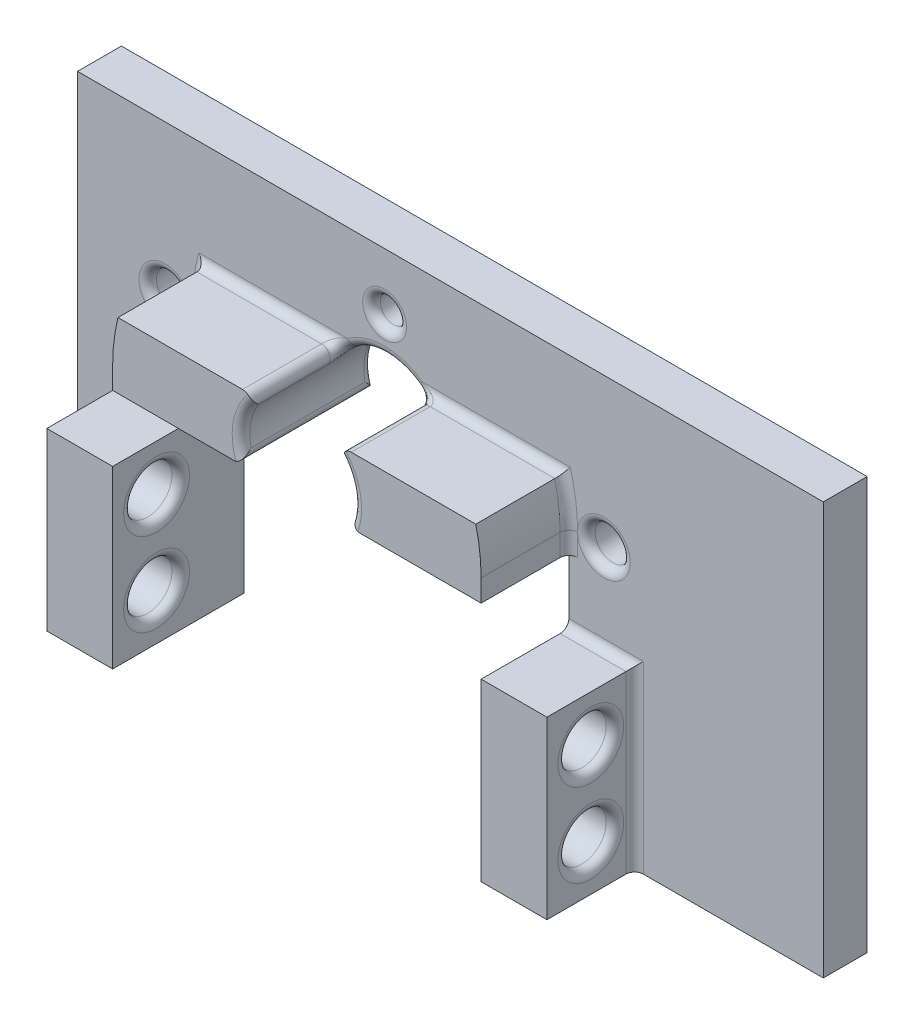
SolidWorks part; units mm, degrees
ref_plane "Front Plane" through (0, 0, 0) normal (0, 0, 1) x (1, 0, 0)
ref_plane "Top Plane" through (0, 0, 0) normal (0, 1, 0) x (1, 0, 0)
ref_plane "Right Plane" through (0, 0, 0) normal (1, 0, 0) x (0, 0, -1)
sketch "Base" plane through (0, 0, 0) normal (0, 0, 1) x (1, 0, 0)
  line L0 (0, 21) -> (0, -21) construction
  line L1 (50, 0) -> (-35, 0) construction
  line L3 (-35, 30) -> (50, 30)
  line L4 (-35, 30) -> (-35, -30)
  line L5 (-35, -30) -> (50, -30)
  line L6 (50, 30) -> (50, -30)
  line L7 (0, 0) -> (0, -30) construction
  circle A0 centre (25, 0) radius 2
  circle A1 centre (0, 0) radius 21
  circle A2 centre (-25, 0) radius 2
  dimension "D1" = 42
  dimension "D2" = 30
  dimension "D3" = 4
  dimension "D4" = 25
  dimension "D5" = 85
  dimension "D6" = 50
sketch "Sketch2" plane through (0, 0, 0) normal (0, 0, 1) x (1, 0, 0)
  line L0 (0, 21) -> (0, -21) construction
  line L1 (50, 0) -> (-35, 0) construction
  line L3 (-35, 30) -> (50, 30) construction
  line L4 (-35, 30) -> (-35, -30) construction
  line L5 (-35, -30) -> (50, -30) construction
  line L6 (50, 30) -> (50, -30) construction
  line L7 (0, 0) -> (0, -30) construction
  line L8 (-30, 12) -> (30, 12)
  line L9 (-30, 12) -> (-30, -20)
  line L10 (-30, -20) -> (30, -20)
  line L11 (30, 12) -> (30, -20)
  circle A0 centre (25, 0) radius 2.5
  circle A1 centre (0, 0) radius 21 construction
  circle A2 centre (-25, 0) radius 2.5
  circle A3 centre (0, 0) radius 6.375
  circle A4 centre (25, -15) radius 2.5
  circle A5 centre (-25, -15) radius 2.5
  circle A6 centre (10.375, 0) radius 1.5
  circle A7 centre (-10.375, 0) radius 1.5
  circle A8 centre (10.375, 0) radius 3.75
  circle A9 centre (-10.375, 0) radius 3.75
  point P25 (25, -17.5)
  point P26 (27.5, -15)
  point P29 (0, -20)
  point P32 (8.875, 0)
  point P33 (6.375, 0)
  point P35 (6.625, 0)
  dimension "D1" = 42
  dimension "D2" = 30
  dimension "D3" = 5
  dimension "D7" = 12.75
  dimension "D11" = 5
  dimension "D14" = 3
  dimension "D8" = 2.5
  dimension "D4" = 25
  dimension "D5" = 85
  dimension "D6" = 50
  dimension "D9" = 15
  dimension "D10" = 25
  dimension "D12" = 2.5
  dimension "D13" = 2.5
  dimension "D15" = 2.25
sketch "Sketch3" plane through (0, 0, 0) normal (0, 0, 1) x (1, 0, 0)
  line L0 (0, 21) -> (0, -21) construction
  line L1 (50, 0) -> (-35, 0) construction
  line L2 (21, 0) -> (21, -30)
  line L3 (-35, 30) -> (50, 30)
  line L4 (-35, 30) -> (-35, -30)
  line L5 (-35, -30) -> (50, -30)
  line L6 (50, 30) -> (50, -30)
  line L7 (0, 0) -> (0, -30) construction
  line L8 (-21, 0) -> (-21, -30)
  line L9 (-20.009, 6.375) -> (20.009, 6.375)
  line L10 (21, -10) -> (28.5, -10)
  line L11 (28.5, -10) -> (28.5, -30)
  line L12 (28.5, -30) -> (21, -30)
  line L13 (-21, -10) -> (-28.5, -10)
  line L14 (-28.5, -10) -> (-28.5, -30)
  line L15 (-28.5, -30) -> (-21, -30)
  line L16 (-35, 17) -> (50, 17)
  line L17 (-21, -2.5) -> (21, -2.5)
  line L18 (-20.3961, 5) -> (-3.9548, 5)
  line L19 (20.3961, 5) -> (3.9548, 5)
  circle A0 centre (25, 0) radius 2
  circle A1 centre (0, 0) radius 21 construction
  circle A2 centre (-25, 0) radius 2
  arc A3 (-21, 0) -> (-20.009, 6.375) centre (0, 0) cw
  circle A4 centre (0, 0) radius 6.375
  arc A5 (21, 0) -> (20.009, 6.375) centre (0, 0) ccw
  circle A6 centre (0, 10.5) radius 1.5
  point P34 (0, 9)
  point P35 (0, 6.375)
  point P38 (0, 12)
  dimension "D1" = 42
  dimension "D2" = 30
  dimension "D3" = 4
  dimension "D7" = 12.75
  dimension "D11" = 3
  dimension "D12" = 10.5
  dimension "D4" = 25
  dimension "D5" = 85
  dimension "D6" = 50
  dimension "D8" = 10
  dimension "D9" = 7.5
  dimension "D10" = 20
  dimension "D13" = 5
  dimension "D14" = 2.5
  dimension "D15" = 7.5
extrude "Boss-Extrude1" add sketch "Sketch3" against normal blind 5 contours A5 L2 L10 L11 L12 L5 L6 L3 L4 L8 L15 L14 L13 A3 L9 A6 A0 A2 | L14 L15 L8 L13 | L12 L11 L10 L2 | A4 L9 A3 L8 L17 | L2 A5 L9 A4 L17 | A4 L9 A3 L18 | L19 A5 L9 A4 region at (21.8128, 2.6346, 0) region at (13.3361, 1.2992, 0) region at (11.4312, 5.7053, 0) region at (24.75, -20, 0) region at (-13.3361, 1.2992, 0) region at (-11.4312, 5.7053, 0) region at (-24.75, -20, 0)
extrude "Boss-Extrude2" add sketch "Sketch3<4>" along normal blind 10 contours L14 L15 L8 L13 | L12 L11 L10 L2 region at (24.75, -20, 0) region at (-24.75, -20, 0)
sketch "Sketch3<4>" plane through (0, 0, 0) normal (0, 0, 1) x (1, 0, 0) same geometry as "Sketch3"
sketch "Sketch4" plane through (28.5, 0, 0) normal (1, 0, 0) x (0, 0, -1)
  line L0 (-5, -10) -> (-5, -30) construction
  line L2 (-10, -10) -> (0, -10) construction
  line L4 (-10, -30) -> (0, -30) construction
  line L5 (-10, -20) -> (0, -20) construction
  line L6 (-10, -10) -> (-10, -30) construction
  line L7 (0, -10) -> (0, -30) construction
  circle A0 centre (-5, -15.25) radius 2.75
  circle A1 centre (-5, -24.75) radius 2.75
  point P14 (-5, -12.5)
  dimension "D1" = 5.5
  dimension "D2" = 2.5
extrude "Cut-Extrude1" cut sketch "Sketch4" against normal up to surface (57 mm away) up to face at (-28.5, -17.5, 6.25)
extrude "Boss-Extrude3" add sketch "Sketch3<5>" along normal blind 10 contours L2 A5 L19 A4 L17 | A4 L18 A3 L8 L17 region at (13.3361, 1.2992, 0) region at (-13.3361, 1.2992, 0)
sketch "Sketch3<5>" plane through (0, 0, 0) normal (0, 0, 1) x (1, 0, 0) same geometry as "Sketch3"
fillet "Fillet1" radius 1 10 edges at (24.75, -10, 0) (28.5, -20, 0) (21, -1.25, 0) (20.8485, 2.5182, 0) (12.1755, 5, 0) (-21, -1.25, 0) (-20.8485, 2.5182, 0) (-12.1755, 5, 0)
fillet "Fillet2" radius 1 10 edges at (3.6072, 5.2563, 0.3315) (0, 6.375, 0) (-3.8026, 5.1167, 0.5311) (0, 6.375, -5) (-5.8644, -2.5, 2.5) (5.8644, -2.5, 2.5) (6.1779, 1.5729, 10) (-6.1779, 1.5729, 10) (3.9548, 5, 5.5) (-3.9548, 5, 5.5)
fillet "Fillet3" radius 1 6 edges at (27, 0, -5) (-23, 0, -5) (1.5, 10.5, -5) (-23, 0, 0) (27, 0, 0) (1.5, 10.5, 0)
fillet "Fillet4" radius 1 8 edges at (-21, -24.75, 7.75) (-28.5, -22, 5) (-21, -15.25, 7.75) (-28.5, -12.5, 5) (28.5, -27.5, 5) (21, -24.75, 7.75) (28.5, -12.5, 5) (21, -15.25, 7.75)
